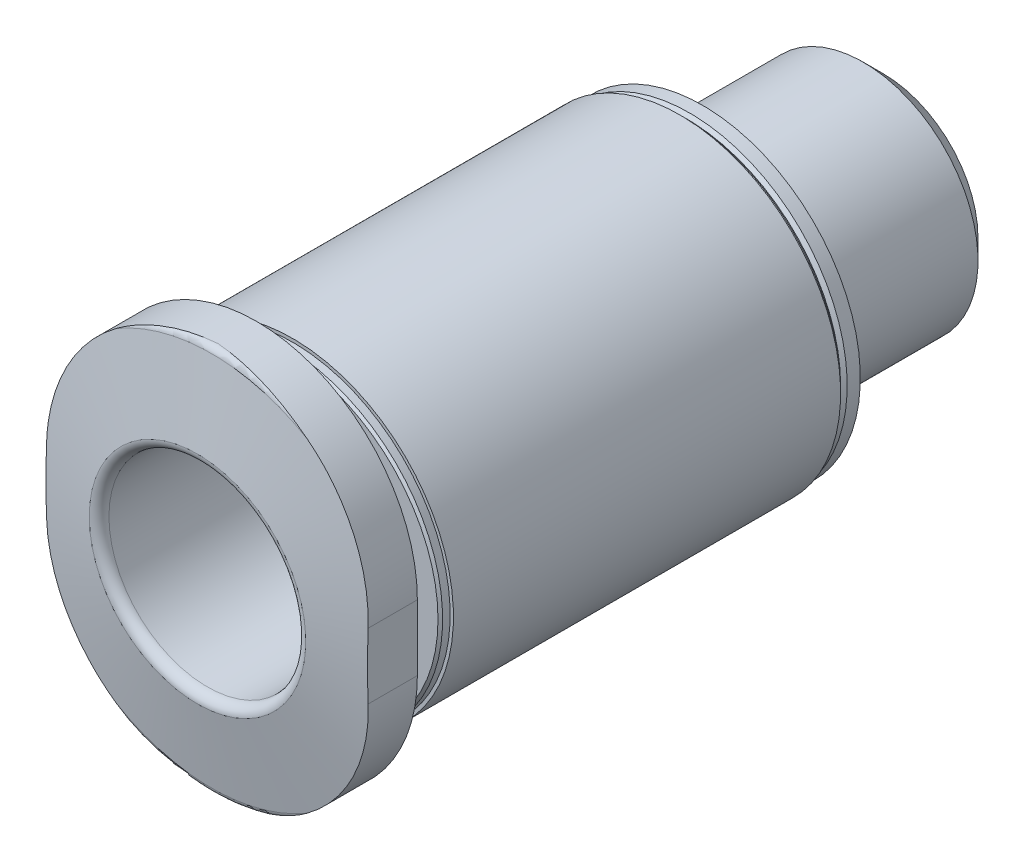
SolidWorks part; units mm, degrees
ref_plane "Front Plane" through (0, 0, 0) normal (0, 0, 1) x (1, 0, 0)
ref_plane "Top Plane" through (0, 0, 0) normal (0, 1, 0) x (1, 0, 0)
ref_plane "Right Plane" through (0, 0, 0) normal (1, 0, 0) x (0, 0, -1)
sketch "Sketch1" plane through (0, 0, 0) normal (1, 0, 0) x (0, 0, -1)
  line L0 (-3.4, 0) -> (-3.4, 3)
  line L1 (-3.4, 3) -> (-15.1, 3)
  line L2 (-15.4, 3.3) -> (-14.9707, 5.7347)
  line L3 (-14.7737, 5.9) -> (-13.6, 5.9)
  line L4 (-13.6, 5.9) -> (-13.6, 4.075)
  line L5 (-13.225, 3.7) -> (-12.8, 3.7)
  line L6 (-12.8, 3.7) -> (-12.8, 4.7293)
  line L7 (-12.8, 4.7293) -> (-12.7293, 4.8)
  line L8 (-12.7293, 4.8) -> (-12.5, 4.8)
  line L9 (-12.5, 4.8) -> (-12.5, 4.9)
  line L10 (-12.5, 4.9) -> (-0.7, 4.9)
  line L11 (-0.7, 4.9) -> (-0.7, 4.8)
  line L12 (-0.7, 4.8) -> (-0.6, 4.8)
  line L13 (-0.6, 4.8) -> (-0.5, 4.7)
  line L14 (-0.5, 4.7) -> (-0.4, 4.8)
  line L15 (-0.4, 4.8) -> (0, 4.8)
  line L16 (0, 4.8) -> (0, 3.5)
  line L17 (0, 3.5) -> (4.8865, 3.5)
  line L18 (4.8865, 3.5) -> (5.5, 2.8865)
  line L19 (5.5, 2.8865) -> (5.5, 0)
  line L20 (5.5, 0) -> (-3.4, 0)
  line L21 (5.5, 0) -> (-3.4, 0) construction
  arc A0 (-15.1, 3) -> (-15.4, 3.3) centre (-15.1, 3.3) cw
  arc A1 (-14.9707, 5.7347) -> (-14.7737, 5.9) centre (-14.7737, 5.7) cw
  arc A2 (-13.6, 4.075) -> (-13.225, 3.7) centre (-13.225, 4.075) ccw
revolve "Revolve1" add sketch "Sketch1" angle 360 about L21
cosmetic thread "Cosmetic Thread1" parameters "D1"=5.5, "D2"=5.773
ref_plane "Plane1" through (0, 0, -5.5) normal (0, 0, 1) x (1, 0, 0)
sketch "Sketch2" plane through (0, 0, -5.5) normal (0, 0, 1) x (1, 0, 0)
  line L0 (-2, -1.1547) -> (0, -2.3094)
  line L1 (0, -2.3094) -> (2, -1.1547)
  line L2 (2, -1.1547) -> (2, 1.1547)
  line L3 (2, 1.1547) -> (0, 2.3094)
  line L4 (0, 2.3094) -> (-2, 1.1547)
  line L5 (-2, 1.1547) -> (-2, -1.1547)
extrude "Cut-Extrude1" cut sketch "Sketch2" along normal blind 8.9
ref_plane "Plane2" through (0, 0, 15.4) normal (0, 0, 1) x (1, 0, 0)
sketch "Sketch3" plane through (0, 0, 15.4) normal (0, 0, 1) x (1, 0, 0)
  line L0 (-10, -10) -> (10, -10)
  line L1 (10, -10) -> (10, 10)
  line L2 (10, 10) -> (-10, 10)
  line L3 (-10, 10) -> (-10, -10)
  line L4 (-4.9, 1) -> (-4.9, -1)
  line L5 (4.9, -1) -> (4.9, 1)
  arc A0 (-4.9, -1) -> (4.9, -1) centre (0, -1) ccw
  arc A1 (4.9, 1) -> (-4.9, 1) centre (0, 1) ccw
extrude "Cut-Extrude2" cut sketch "Sketch3" against normal blind 2
ref_plane "Plane3" through (0, 0, 20.9) normal (0, 0, 1) x (1, 0, 0)
ref_plane "Plane4" through (0, 0, 9.4) normal (0, 0, 1) x (1, 0, 0)
ref_plane "Plane5" through (0, 0, -6) normal (0, 0, 1) x (1, 0, 0)
ref_plane "Plane6" through (0, 0, 3.4) normal (0, 0, 1) x (1, 0, 0)
ref_plane "ANBAU XY" through (0, 0, 0) normal (0, 0, -1) x (-1, 0, 0)
ref_plane "ANBAU XZ" through (0, 0, 0) normal (0, 1, 0) x (1, 0, 0)
ref_plane "ANBAU YZ" through (0, 0, 0) normal (1, 0, 0) x (0, 0, -1)
ref_axis "ANBAU X" through (-80.9, 0, 0) along (1, 0, 0)
ref_axis "ANBAU Y" through (0, 50, 0) along (0, -1, 0)
ref_axis "ANBAU Z" through (0, 0, -80.9) along (0, 0, 1)
sketch3d "ANBAU"
  point P0 (0, 0, 0)
ref_plane "ANBAU_STD XY" through (0, 0, 0) normal (0, 0, 1) x (1, 0, 0)
ref_plane "ANBAU_STD XZ" through (0, 0, 0) normal (0, -1, 0) x (-1, 0, 0)
ref_plane "ANBAU_STD YZ" through (0, 0, 0) normal (1, 0, 0) x (0, 0, -1)
ref_axis "ANBAU_STD X" through (-80.9, 0, 0) along (1, 0, 0)
ref_axis "ANBAU_STD Y" through (0, -50, 0) along (0, 1, 0)
ref_axis "ANBAU_STD Z" through (0, 0, 80.9) along (0, 0, -1)
sketch3d "ANBAU_STD"
  point P0 (0, 0, 0)
ref_plane "CPV XY" through (0, 0, 0) normal (0, 0, 1) x (1, 0, 0)
ref_plane "CPV XZ" through (0, 0, 0) normal (0, -1, 0) x (-1, 0, 0)
ref_plane "CPV YZ" through (0, 0, 0) normal (1, 0, 0) x (0, 0, -1)
ref_axis "CPV X" through (-80.9, 0, 0) along (1, 0, 0)
ref_axis "CPV Y" through (0, -50, 0) along (0, 1, 0)
ref_axis "CPV Z" through (0, 0, 80.9) along (0, 0, -1)
sketch3d "CPV"
  point P0 (0, 0, 0)
ref_plane "PUN XY" through (0, 0, 3.4) normal (0, 0, -1) x (-1, 0, 0)
ref_plane "PUN XZ" through (0, 0, 0) normal (0, 1, 0) x (1, 0, 0)
ref_plane "PUN YZ" through (0, 0, 0) normal (1, 0, 0) x (0, 0, -1)
ref_axis "PUN X" through (-80.9, 0, 3.4) along (1, 0, 0)
ref_axis "PUN Y" through (0, 50, 3.4) along (0, -1, 0)
ref_axis "PUN Z" through (0, 0, -80.9) along (0, 0, 1)
sketch3d "PUN"
  point P0 (0, 0, 3.4)
